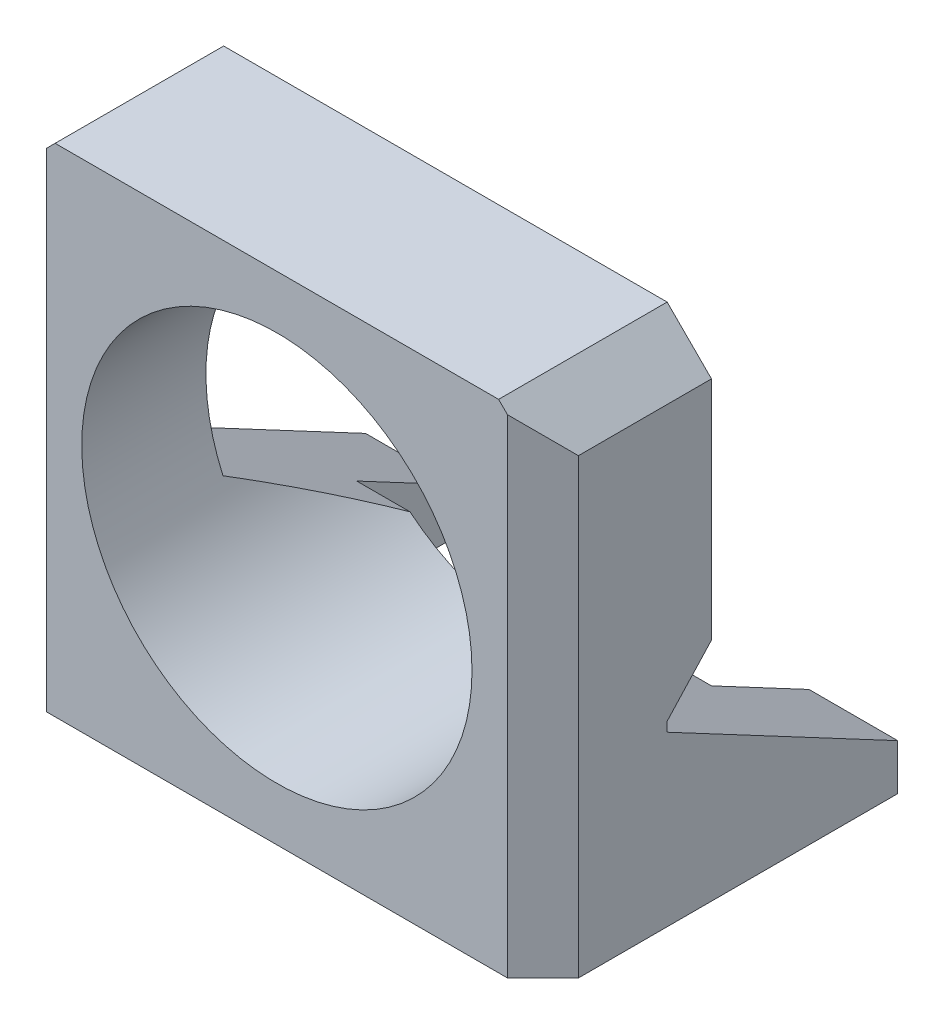
SolidWorks part; units mm, degrees
ref_plane "Front Plane" through (0, 0, 0) normal (0, 0, 1) x (1, 0, 0)
ref_plane "Top Plane" through (0, 0, 0) normal (0, 1, 0) x (1, 0, 0)
ref_plane "Right Plane" through (0, 0, 0) normal (1, 0, 0) x (0, 0, -1)
sketch "Sketch1" plane through (0, 0, 0) normal (0, 0, 1) x (1, 0, 0)
  line L0 (-15, 11.5) -> (-12.5, 14)
  line L1 (-12.5, 14) -> (12.5, 14)
  line L2 (-15, 11.5) -> (-15, -14)
  line L3 (-15, -14) -> (15, -14)
  line L4 (15, 11.5) -> (15, -14)
  line L5 (-15, 14) -> (15, -14) construction
  line L6 (-15, -14) -> (15, 14) construction
  line L7 (12.5, 14) -> (15, 11.5)
  circle A0 centre (0, 0) radius 11
  dimension "D1" = 22
  dimension "D2" = 30
  dimension "D3" = 28
extrude "Boss-Extrude1" add sketch "Sketch1" along normal blind 7
sketch "Sketch2" plane through (0, 0, 0) normal (0, 0, -1) x (-1, 0, 0)
  line L0 (0, 0) -> (0, -50000) construction
  line L1 (-15, -14) -> (-10, -14)
  line L2 (-15, -14) -> (-15, -11.5)
  line L3 (-15, -11.5) -> (-10, -11.5)
  line L4 (-10, -14) -> (-10, -11.5)
  line L5 (15, -11.5) -> (10, -11.5)
  line L6 (10, -14) -> (10, -11.5)
  line L7 (15, -14) -> (10, -14)
  line L8 (15, -14) -> (15, -11.5)
  dimension "D1" = 2.5
  dimension "D2" = 5
extrude "Boss-Extrude2" add sketch "Sketch2" along normal blind 13 contours L5 L6 L7 L8 | L2 L3 L4 L1
chamfer "Chamfer2" distance 2 angle 45 2 edges at (-10, -12.75, 0) (10, -12.75, 0)
sketch "Sketch5" plane through (0, -14, 0) normal (0, -1, 0) x (1, 0, 0)
  line L0 (-10, -7.5) -> (10, -7.5)
  line L1 (-10, -13) -> (-10, -2) construction
  line L2 (10, -13) -> (10, -2) construction
  line L3 (10, -7.5) -> (10, -2)
  line L4 (10, -2) -> (8, 0)
  line L5 (8, 0) -> (-8, 0)
  line L6 (-8, 0) -> (-10, -2)
  line L7 (-10, -2) -> (-10, -7.5)
  line M5 (-10, -13) -> (-10, -2)
  line M6 (-10, -2) -> (-8, 0)
  line M7 (-8, 0) -> (8, 0)
  line M8 (8, 0) -> (10, -2)
  line M9 (10, -2) -> (10, -13)
extrude "Boss-Extrude6" add sketch "Sketch5" against normal up to surface (2.5 mm away) contours L0 M5 M9 M8 M7 M6 region at (0, -14, -3.8345) up to face at (11.6, -11.5, -5.6)
chamfer "Chamfer3" distance 2 angle 45 1 edges at (15, -1.25, 7)
chamfer "Chamfer4" distance 2 angle 45 1 edges at (-15, -1.25, 7)
sketch "Sketch4" plane through (0, 0, 0) normal (0, 0, -1) x (-1, 0, 0)
  line L8 (0, 0) -> (0, 50000) construction
  line L14 (-15, -1.25) -> (15, 11.5)
  line L15 (15, 11.5) -> (12.5, 14)
  line L16 (12.5, 14) -> (-12.5, 14)
  line L17 (-12.5, 14) -> (-15, 11.5)
  line L18 (-15, 11.5) -> (-15, -1.25)
  line L19 (-15, 11.5) -> (-15, -14) construction
  point P8 (-15, -1.25)
extrude "Boss-Extrude4" add sketch "Sketch4" along normal blind 2.5
chamfer "Chamfer6" distance 2.5 2 edges at (12.9953, -0.398, 0) (-11.1504, 9.8639, 0)
chamfer "Chamfer7" distance 7 angle 62 1 edges at (0, -11.5, 0) first distance on face at (-0.5726, -4.3777, 0)
